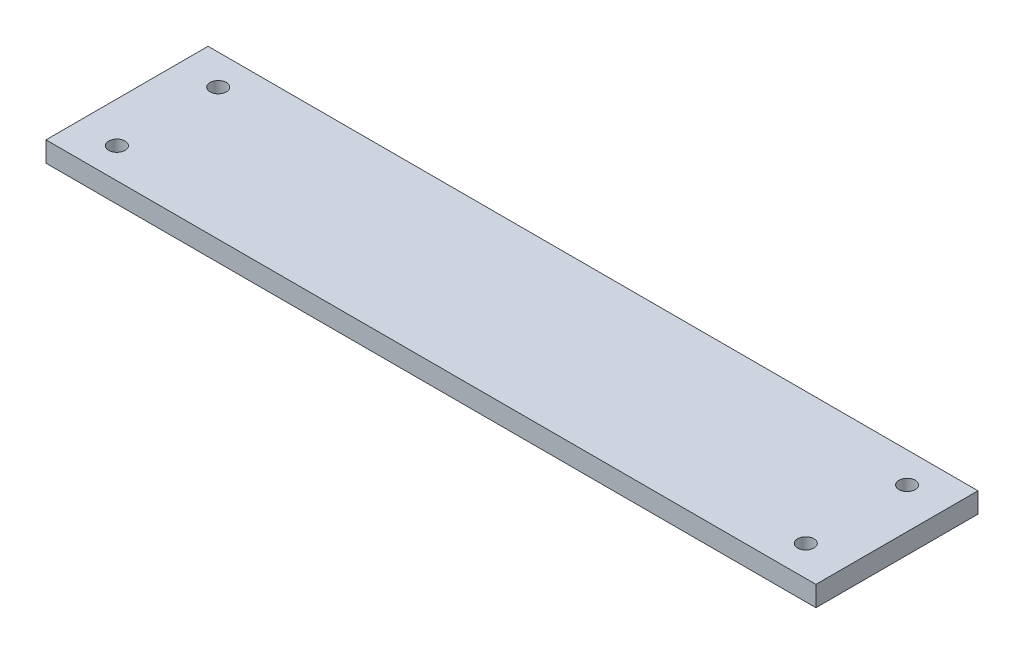
SolidWorks part; units mm, degrees
material "6061-T6 (SS)"
ref_plane "Front" through (0, 0, 0) normal (0, 0, 1) x (1, 0, 0)
ref_plane "Top" through (0, 0, 0) normal (0, 1, 0) x (1, 0, 0)
ref_plane "Right" through (0, 0, 0) normal (1, 0, 0) x (0, 0, -1)
sketch "Sketch1" plane through (0, 0, 0) normal (0, 1, 0) x (1, 0, 0)
  line L0 (241.3, 0) -> (241.3, 19.05) construction
  line L1 (0, 0) -> (241.3, 0)
  line L2 (0, 0) -> (0, 50.8)
  line L3 (0, 50.8) -> (241.3, 50.8)
  line L4 (241.3, 0) -> (241.3, 50.8)
  dimension "D1" = 50.8
extrude "Boss-Extrude1" add sketch "Sketch1" along normal blind 6.35
sketch "Sketch4" plane through (0, 6.35, 0) normal (0, 1, 0) x (1, 0, 0)
  line L0 (0, 0) -> (12.7, 9.525) construction
  line L1 (0, 0) -> (241.3, 0) construction
  line L6 (12.7, 9.525) -> (12.7, 41.275) construction
  line L7 (12.7, 41.275) -> (25.4, 50.8) construction
  line L8 (241.3, 50.8) -> (0, 50.8) construction
  line L9 (120.65, 0) -> (120.65, 19.6096) construction
  point P0 (12.7, 41.275)
  point P4 (12.7, 9.525)
  point P34 (228.6, 9.525)
  point P36 (228.6, 41.275)
  dimension "D1" = 31.75
  dimension "D2" = 25.4
hole_wizard "#10 Clearance Hole1" positions "Sketch4" profile "Sketch3" hole size "#10" standard "ANSI Inch" end condition up to next
sketch "Sketch3" plane through (12.7, 6.35, -41.275) normal (1, 0, 0) x (0, 0, 1)
  line L0 (0, 0) -> (0, 6.35)
  line L1 (0, 6.35) -> (2.5527, 6.35)
  line L2 (2.5527, 6.35) -> (2.5527, 0)
  line L5 (2.5527, 0) -> (0, 0)
  line L11 (0, -6.35) -> (0, 107.95) construction
  dimension "Thru Hole Dia." = 5.1054
  dimension "Thru Hole Depth" = 6.35
